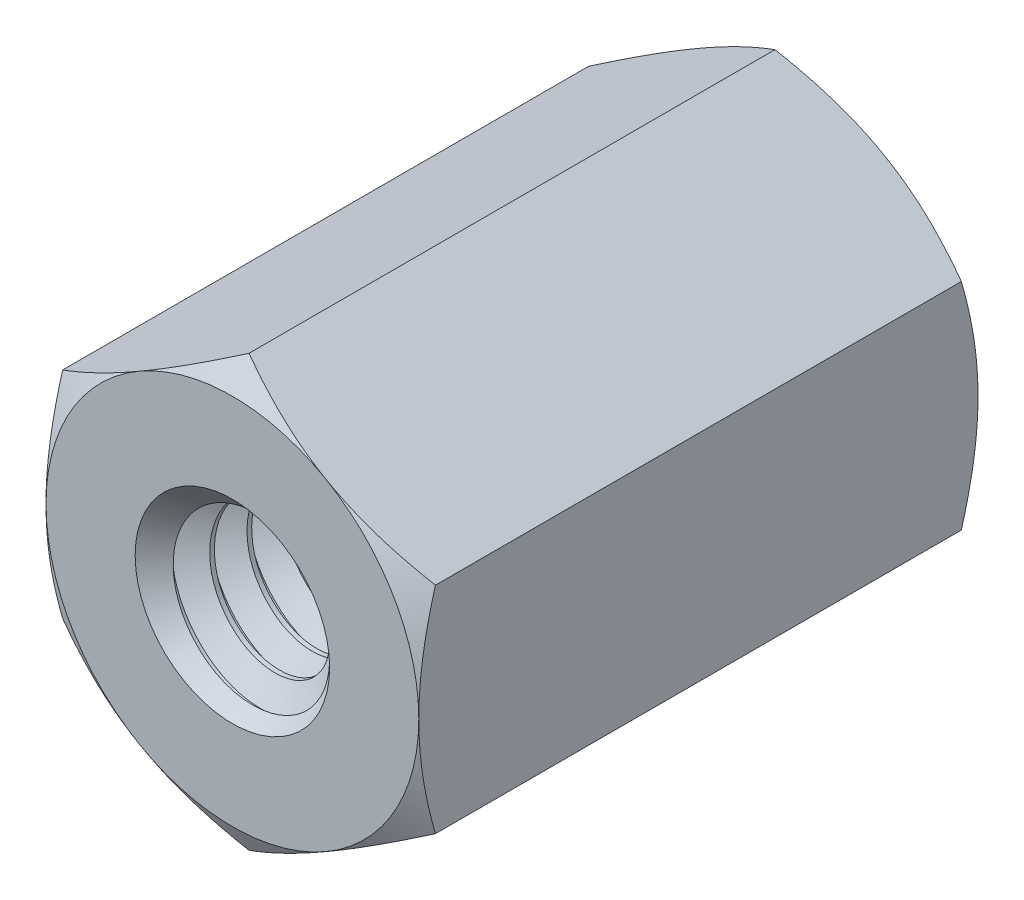
SolidWorks part; units mm, degrees
ref_plane "Front Plane" through (0, 0, 0) normal (0, 0, 1) x (1, 0, 0)
ref_plane "Top Plane" through (0, 0, 0) normal (0, 1, 0) x (1, 0, 0)
ref_plane "Right Plane" through (0, 0, 0) normal (1, 0, 0) x (0, 0, -1)
sketch "Sketch1" plane through (0, 0, 0) normal (1, 0, 0) x (0, 0, -1)
  line L0 (0, -2) -> (0, 2) construction
  line L1 (0, 0) -> (6, 0) construction
  line L2 (0, -1) -> (0, 1) construction
  line L3 (-0.375, 1.0433) -> (0.025, 1.0433) construction
  line L4 (0.025, 1.0433) -> (-0.175, 0.6969) construction
  line L5 (-0.175, 0.6969) -> (-0.375, 1.0433) construction
  line L6 (-0.3625, 1.0217) -> (0.0125, 1.0217) construction
  line L7 (-0.35, 1) -> (0, 1) construction
  line L8 (-0.2, 0.7402) -> (-0.15, 0.7402) construction
  line L9 (-0.175, 0.7402) -> (-0.175, 0.6969) construction
  line L10 (-0.175, 1) -> (-0.175, 1.0433) construction
  point P4 (0, 0)
  point P10 (0, 0)
  point P12 (0, -1)
  point P23 (-0.175, 1.0217)
  dimension "Hex" = 4
  dimension "Length" = 6
  dimension "Thread OD" = 2
  dimension "D1" = 60
  dimension "Pitch" = 0.4
  dimension "D2" = 0.05
sketch "Sketch2" plane through (0, 0, 0) normal (0, 0, 1) x (1, 0, 0)
  line L1 (-2, 1.1547) -> (-2, -1.1547)
  line L2 (-2, -1.1547) -> (0, -2.3094)
  line L3 (0, -2.3094) -> (2, -1.1547)
  line L4 (2, -1.1547) -> (2, 1.1547)
  line L5 (2, 1.1547) -> (0, 2.3094)
  line L6 (0, 2.3094) -> (-2, 1.1547)
  circle A0 centre (0, 0) radius 2 construction
  circle A1 centre (0, 0) radius 1
extrude "Boss-Extrude1" add sketch "Sketch2" against normal up to vertex (6 mm away) up to point (0, 0, -6)
sketch "Sketch3" plane through (0, 0, 0) normal (0, 0, 1) x (1, 0, 0)
  circle A0 centre (0, 0) radius 2 construction
  circle A1 centre (0, 0) radius 2
extrude "Cut-Extrude2" cut sketch "Sketch3" against normal through all draft 60 flip side to cut
sketch "Sketch4" plane through (0, 0, -6) normal (0, 0, -1) x (-1, 0, 0)
  circle A0 centre (0, 0) radius 2 construction
  circle A1 centre (0, 0) radius 2
extrude "Cut-Extrude3" cut sketch "Sketch4" against normal through all draft 60 flip side to cut
sketch "Sketch5" plane through (0, 0, 0) normal (0, 0, 1) x (1, 0, 0)
  circle A0 centre (0, 0) radius 1 construction
  circle A1 centre (0, 0) radius 1
ref_axis "Center Axis 1" through (0, 0, -57.7835) along (0, 0, 1)
curve "Helix/Spiral1" pitch 0.4 height 6.4 radius 1 centre (0, 0, 0) axis (0, 0, -1) start towards (0, 1, 0)
sketch "Sketch6" plane through (0, 0, 0) normal (1, 0, 0) x (0, 0, -1)
  line L0 (-0.3625, 1.0217) -> (0.0125, 1.0217)
  line L1 (0.0125, 1.0217) -> (-0.15, 0.7402)
  line L2 (-0.15, 0.7402) -> (-0.2, 0.7402)
  line L3 (-0.2, 0.7402) -> (-0.3625, 1.0217)
sweep "Sweep1" add profiles "Sketch6" path "Helix/Spiral1"
sketch "Sketch7" plane through (0, 0, 0) normal (0, 0, 1) x (1, 0, 0)
  circle A0 centre (0, 0) radius 1.0433
extrude "Cut-Extrude4" cut sketch "Sketch7" along normal through all and the other way through all draft 45
sketch "Sketch8" plane through (0, 0, -6) normal (0, 0, -1) x (-1, 0, 0)
  circle A0 centre (0, 0) radius 1.0433
extrude "Cut-Extrude5" cut sketch "Sketch8" along normal through all and the other way through all draft 45
equation "\"D2@Sketch1\"=\"Pitch@Sketch1\"/8"
equation "\"D4@Helix/Spiral1\"=\"Pitch@Sketch1\""
equation "\"D3@Helix/Spiral1\"=\"Length@Sketch1\"+\"Pitch@Sketch1\""
